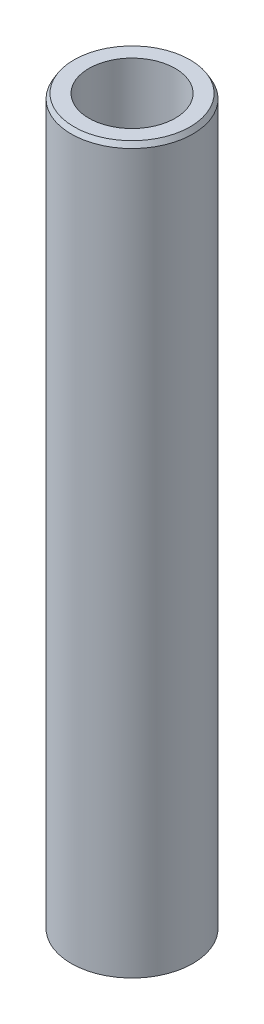
SolidWorks part; units mm, degrees
ref_plane "Front Plane" through (0, 0, 0) normal (0, 0, 1) x (1, 0, 0)
ref_plane "Top Plane" through (0, 0, 0) normal (0, 1, 0) x (1, 0, 0)
ref_plane "Right Plane" through (0, 0, 0) normal (1, 0, 0) x (0, 0, -1)
sketch "Sketch1" plane through (0, 0, 0) normal (0, 1, 0) x (1, 0, 0)
  circle A0 centre (0, 0) radius 40
  dimension "SHAFT_OD" = 80
extrude "Boss-Extrude1" add sketch "Sketch1" along normal blind 477.3131
sketch "Sketch2" plane through (0, 0, 0) normal (0, 1, 0) x (1, 0, 0)
  circle A0 centre (0, 0) radius 28.3904
  dimension "BORE_D" = 56.7809
extrude "Cut-Extrude1" cut sketch "Sketch2" along normal through all
chamfer "Chamfer1" distance 3.1734 angle 30 2 edges at (0, 477.3131, 40) (0, 0, 40) first distance on face at (0, 477.3131, 40) first distance on face at (0, 0, 28.3904)
